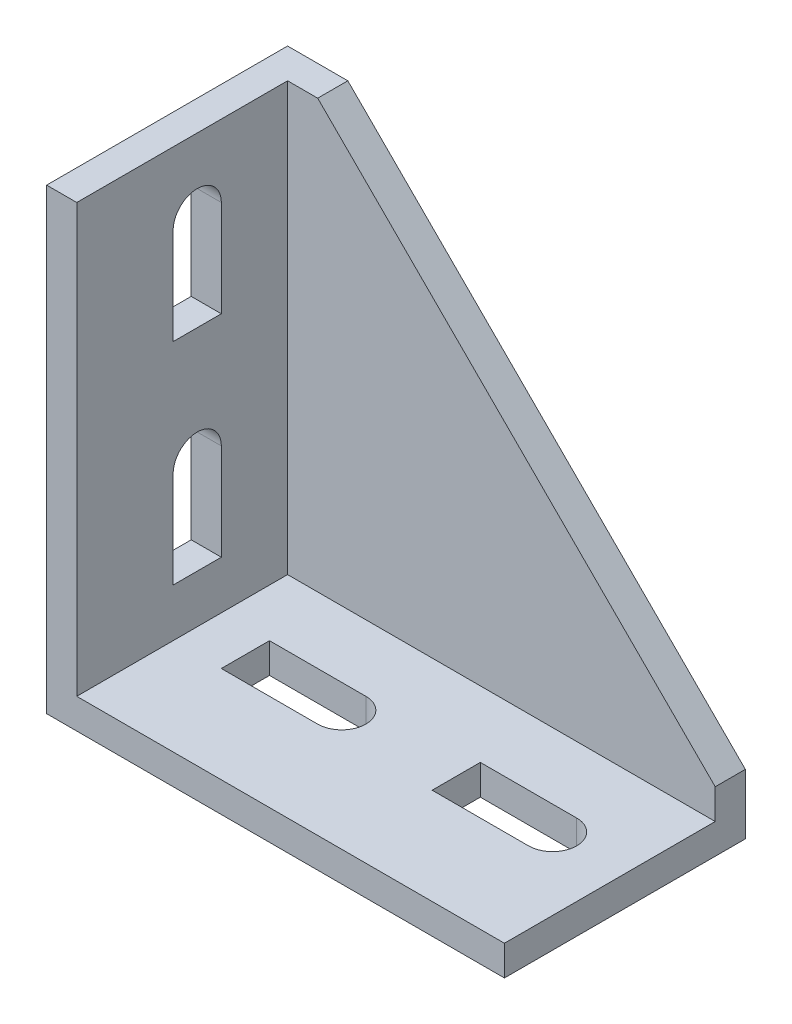
SolidWorks part; units mm, degrees
material "6063-T6"
ref_plane "Front Plane" through (0, 0, 0) normal (0, 0, 1) x (1, 0, 0)
ref_plane "Top Plane" through (0, 0, 0) normal (0, 1, 0) x (1, 0, 0)
ref_plane "Right Plane" through (0, 0, 0) normal (1, 0, 0) x (0, 0, -1)
sketch "Sketch1" plane through (0, 0, 0) normal (0, 0, 1) x (1, 0, 0)
  line L0 (0, 76) -> (0, 0)
  line L1 (0, 0) -> (76, 0)
  line L2 (76, 0) -> (76, 10)
  line L3 (76, 10) -> (10, 76)
  line L4 (10, 76) -> (0, 76)
  dimension "D1" = 76
  dimension "D2" = 10
extrude "Boss-Extrude1" add sketch "Sketch1" along normal blind 40
sketch "Sketch2" plane through (0, 0, 40) normal (0, 0, 1) x (1, 0, 0)
  line L2 (5, 76) -> (76, 76)
  line L3 (76, 76) -> (76, 5)
  line L4 (5, 5) -> (76, 5)
  line L5 (5, 76) -> (5, 5)
  line L6 (5, 5) -> (76, 5)
  line L7 (5, 76) -> (5, 5)
  dimension "D1" = 5
extrude "Cut-Extrude1" cut sketch "Sketch2" against normal offset from surface (35 mm away) 5 up to face at (32.4, 32.4, 0)
sketch "Sketch3" plane through (0, 5, 0) normal (0, 1, 0) x (1, 0, 0)
  line L0 (76, -20) -> (23, -20) construction
  line L1 (76, -40) -> (76, 0) construction
  line L2 (76, -5) -> (76, -40) construction
  line L3 (13, -16) -> (33, -16)
  line L4 (13, -16) -> (13, -24)
  line L5 (13, -24) -> (33, -24)
  line L6 (33, -16) -> (33, -24)
  line L7 (23, -24) -> (23, -16) construction
  line L8 (13, -20) -> (33, -20) construction
  line L9 (48, -16) -> (68, -16)
  line L10 (48, -16) -> (48, -24)
  line L11 (48, -24) -> (68, -24)
  line L12 (68, -16) -> (68, -24)
  line L13 (58, -24) -> (58, -16) construction
  line L14 (48, -20) -> (68, -20) construction
  point P7 (58, -20)
  dimension "D1" = 8
  dimension "D2" = 20
  dimension "D3" = 8
  dimension "D4" = 15
extrude "Cut-Extrude2" cut sketch "Sketch3" against normal mid plane 45
pattern_circular "CirPattern1" count 2 over 90 about axis through (0, 0, 40) along (0, 0, -1) of "Cut-Extrude2" reverse direction yes
fillet "Fillet1" radius 4 8 edges at (68, 2.5, 24) (68, 2.5, 16) (33, 2.5, 24) (33, 2.5, 16) (2.5, 33, 24) (2.5, 33, 16) (2.5, 68, 24) (2.5, 68, 16)
